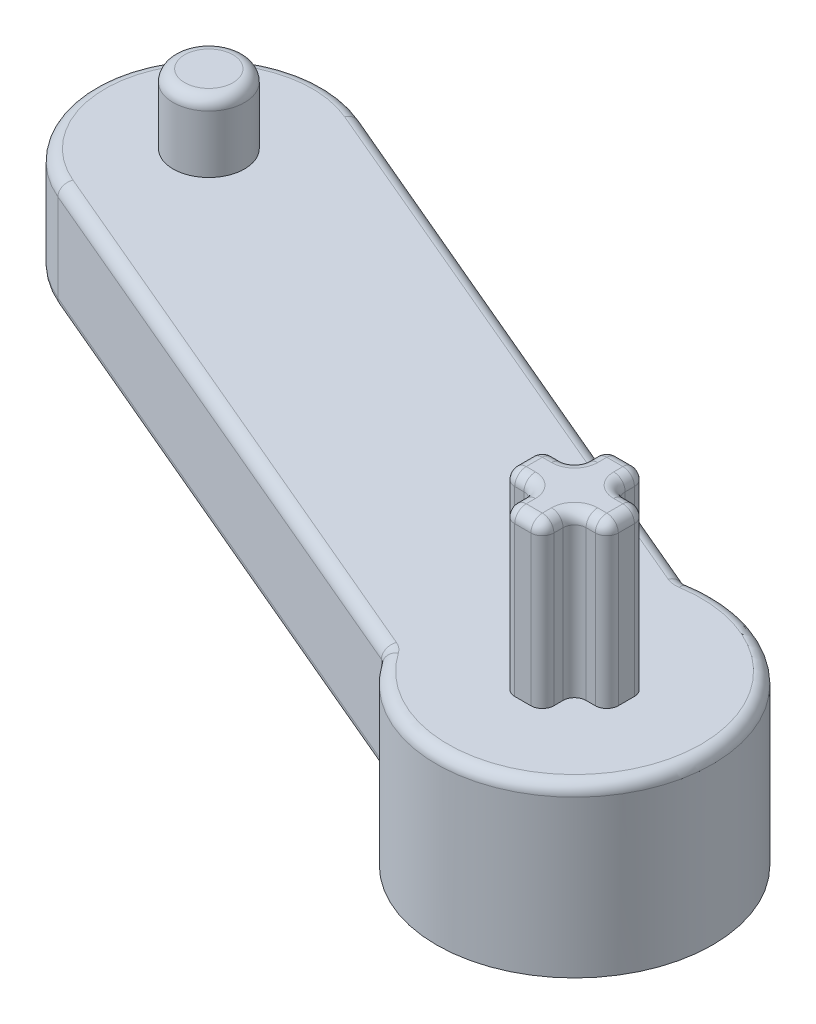
SolidWorks part; units mm, degrees
ref_plane "Front Plane" through (0, 0, 0) normal (0, 0, 1) x (1, 0, 0)
ref_plane "Top Plane" through (0, 0, 0) normal (0, 1, 0) x (1, 0, 0)
ref_plane "Right Plane" through (0, 0, 0) normal (1, 0, 0) x (0, 0, -1)
sketch "Sketch1" plane through (0, 0, 0) normal (0, 1, 0) x (1, 0, 0)
  line L1 (1.2678, 4.2969) -> (-1.2678, 4.2969) construction
  line L2 (1.2678, 4.2969) -> (1.2678, 2.6969) construction
  line L3 (1.2678, 2.6969) -> (-1.2678, 2.6969) construction
  line L4 (-1.2678, 4.2969) -> (-1.2678, 2.6969) construction
  line L5 (1.2678, 4.2969) -> (-1.2678, 2.6969) construction
  line L6 (1.2678, 2.6969) -> (-1.2678, 4.2969) construction
  line L7 (1.5678, 4.5156) -> (1.5678, 2.8811)
  line L8 (-1.5678, 2.8811) -> (-1.5678, 4.5156)
  line L10 (-1.5678, 4.5156) -> (-1.5678, 2.6969) construction
  circle A0 centre (0, 0) radius 2.98 construction
  arc A1 (-1.2678, 4.2969) -> (1.2678, 4.2969) centre (0, 0) cw construction
  arc A2 (1.2678, 2.6969) -> (-1.2678, 2.6969) centre (0, 0) cw construction
  arc A3 (-1.5678, 4.5156) -> (1.5678, 4.5156) centre (0, 0) cw
  arc A4 (-1.5678, 2.8811) -> (1.5678, 2.8811) centre (0, 0) ccw
  arc A5 (1.5678, 2.8811) -> (-1.3954, 2.9684) centre (0, 0) cw construction
  circle A6 centre (0, 0) radius 5.5
  circle A7 centre (0, 0) radius 4.78 construction
  point P3 (0, 3.4969)
  dimension "D1" = 1.6
  dimension "D3" = 5.96
  dimension "D5" = 11
  dimension "D2" = 4.48
  dimension "D4" = 0.3
extrude "Boss-Extrude1" add sketch "Sketch1" along normal blind 5.3
sketch "Sketch2" plane through (0, 5.3, 0) normal (0, 1, 0) x (1, 0, 0)
  circle A0 centre (0, 0) radius 6
  dimension "D1" = 12
extrude "Boss-Extrude2" add sketch "Sketch2" along normal blind 0.5
sketch "Sketch3" plane through (0, 5.8, 0) normal (0, 1, 0) x (1, 0, 0)
  line L0 (-0.85, -2.25) -> (-0.85, -0.85)
  line L1 (0.85, -2.25) -> (-0.85, -2.25)
  line L2 (0.85, -2.25) -> (0.85, 2.25) construction
  line L3 (0.85, 2.25) -> (-0.85, 2.25)
  line L4 (-0.85, -2.25) -> (-0.85, 2.25) construction
  line L5 (0.85, -2.25) -> (-0.85, 2.25) construction
  line L6 (0.85, 2.25) -> (-0.85, -2.25) construction
  line L7 (2.25, -0.85) -> (-2.25, -0.85) construction
  line L8 (2.25, -0.85) -> (2.25, 0.85)
  line L9 (2.25, 0.85) -> (-2.25, 0.85) construction
  line L10 (-2.25, -0.85) -> (-2.25, 0.85)
  line L11 (2.25, -0.85) -> (-2.25, 0.85) construction
  line L12 (2.25, 0.85) -> (-2.25, -0.85) construction
  line L13 (-0.85, -0.85) -> (-2.25, -0.85)
  line L14 (-2.25, 0.85) -> (-0.85, 0.85)
  line L15 (-0.85, 0.85) -> (-0.85, 2.25)
  line L16 (0.85, 2.25) -> (0.85, 0.85)
  line L17 (0.85, 0.85) -> (2.25, 0.85)
  line L18 (2.25, -0.85) -> (0.85, -0.85)
  line L19 (0.85, -0.85) -> (0.85, -2.25)
  line L21 (4, -4) -> (-4, -4) construction
  line L22 (4, -4) -> (4, 4) construction
  line L23 (4, 4) -> (-4, 4) construction
  line L24 (-4, -4) -> (-4, 4) construction
  line L25 (4, -4) -> (-4, 4) construction
  line L26 (4, 4) -> (-4, -4) construction
  circle A0 centre (-4, -4) radius 2.2 construction
  circle A1 centre (-4, 4) radius 2.2 construction
  circle A2 centre (4, 4) radius 2.2 construction
  circle A3 centre (4, -4) radius 2.2 construction
  point P0 (0, 0)
  point P6 (0, 0)
  point P11 (0, 0)
  dimension "D4" = 4.4
  dimension "D1" = 4.5
  dimension "D2" = 1.7
  dimension "D3" = 8
extrude "Boss-Extrude3" add sketch "Sketch3" along normal blind 8
sketch "Sketch4" plane through (0, 5.3, 0) normal (0, -1, 0) x (1, 0, 0)
  circle A0 centre (0, 0) radius 6
  circle A1 centre (0, 0) radius 5.5
  circle A2 centre (0, 0) radius 5.5 construction
  circle A3 centre (0, 0) radius 6 construction
extrude "Boss-Extrude4" add sketch "Sketch4" along normal up to surface (5.3 mm away) up to face at (0, 0, 5.5)
sketch "Sketch5" plane through (0, 13.8, 0) normal (0, 1, 0) x (1, 0, 0)
  circle A0 centre (0, 0) radius 2.4052
extrude "Cut-Extrude1" cut sketch "Sketch5" against normal blind 1
sketch "Sketch6" plane through (0, 0, 0) normal (0, -1, 0) x (1, 0, 0)
  line L0 (0, 0) -> (-15.3335, -6.5103) construction
  line L1 (-29.5682, -7.1221) -> (-25.66, -16.3268) construction
  line L2 (-29.5682, -7.1221) -> (-5.0069, 3.3062)
  line L3 (-5.0069, 3.3062) -> (-1.0988, -5.8985) construction
  line L4 (-25.66, -16.3268) -> (-1.0988, -5.8985)
  line L5 (-29.5682, -7.1221) -> (-1.0988, -5.8985) construction
  line L6 (-5.0069, 3.3062) -> (-25.66, -16.3268) construction
  line L7 (-5.5228, -2.3449) -> (-27.6141, -11.7244) construction
  circle A0 centre (0, 0) radius 6 construction
  arc A2 (-29.5682, -7.1221) -> (-25.66, -16.3268) centre (-27.6141, -11.7244) ccw
  arc A3 (-1.0988, -5.8985) -> (-5.0069, 3.3062) centre (0, 0) cw
  arc A5 (-28.7737, -3.0286) -> (-28.2774, -3.525) centre (-24.9987, 0.25) ccw construction
  point P0 (-15.3335, -6.5103)
  circle M3 centre (0, 0) radius 6
  dimension "D2" = 10
  dimension "D1" = 30
extrude "Boss-Extrude5" add sketch "Sketch6" against normal up to surface (5.8 mm away) contours L2 A2 L4 M3 | L2 A2 L4 A3 region at (-18.0205, 0, -7.6512) up to face at (0, 5.8, 0)
sketch "Sketch7" plane through (0, 5.8, 0) normal (0, 1, 0) x (1, 0, 0)
  circle A0 centre (-27.6141, 11.7244) radius 1.55
  dimension "D1" = 3.1
extrude "Boss-Extrude6" add sketch "Sketch7" along normal blind 3
sketch "Sketch9" plane through (0, 0, 0) normal (0, -1, 0) x (1, 0, 0)
  line L0 (-1.5678, -4.5156) -> (-1.5678, -2.8811) construction
  line L1 (-1.5678, -2.8811) -> (-1.5678, -4.5156)
  line L2 (1.5678, -2.8811) -> (1.5678, -4.5156)
  arc A0 (1.5678, -2.8811) -> (-1.5678, -2.8811) centre (0, 0) ccw
  arc A1 (1.5678, -4.5156) -> (-1.5678, -4.5156) centre (0, 0) cw
  arc A2 (-1.5678, -4.5156) -> (1.5678, -4.5156) centre (0, 0) ccw construction
  circle A3 centre (0, 0) radius 6
  dimension "D1" = 12
extrude "Boss-Extrude7" add sketch "Sketch9" along normal up to surface (1.5 mm away)
sketch "Sketch10" plane through (0, 0, 0) normal (0, -1, 0) x (1, 0, 0)
  line L1 (-1.0988, -5.8985) -> (-25.66, -16.3268)
  line L2 (-5.0069, 3.3062) -> (-29.5682, -7.1221)
  arc A0 (-5.0069, 3.3062) -> (-1.0988, -5.8985) centre (0, 0) ccw
  arc A1 (-25.66, -16.3268) -> (-29.5682, -7.1221) centre (-27.6141, -11.7244) cw
  arc A2 (-5.0069, 3.3062) -> (-1.0988, -5.8985) centre (0, 0) ccw construction
extrude "Cut-Extrude2" cut sketch "Sketch10" against normal blind 1
fillet "Fillet1" radius 0.5 39 edges at (-0.85, 9.3, 0.85) (0.85, 9.3, -2.25) (2.25, 9.3, -0.85) (0.85, 9.3, -0.85) (-0.85, 9.3, -0.85) (-0.85, 9.3, -2.25) (2.25, 9.3, 0.85) (0.85, 9.3, 2.25) (-2.25, 9.3, -0.85) (-0.85, 9.3, 2.25) (-2.25, 9.3, 0.85) (-1.5678, 1.9, -2.8811) (-1.5678, 1.9, -4.5156) (1.5678, 1.9, -4.5156) (1.5678, 1.9, -2.8811) (0.85, 9.3, 0.85) (0, 12.8, -2.25) (0.85, 12.8, -1.55) (1.55, 12.8, -0.85) (2.25, 12.8, 0) (1.55, 12.8, 0.85) (0.85, 12.8, 1.55) (0, 12.8, 2.25) (-0.85, 12.8, 1.55) (-1.55, 12.8, 0.85) (-2.25, 12.8, 0) (-1.55, 12.8, -0.85) (-0.85, 12.8, -1.55) (5.5228, 5.8, 2.3449) (-17.2875, 5.8, -1.908) (-32.2164, 5.8, -13.6785) (-27.6141, 8.8, -10.1744) (-13.3794, 5.8, -11.1127) (-1.0988, 3.4, -5.8985) (-5.0069, 3.4, 3.3062) (-13.3794, 1, -11.1127) (-32.2164, 1, -13.6785) (-17.2875, 1, -1.908) (-5.5228, 1, -2.3449)
equation "\"Bearing Inner Diameter\"= 3.1mm"
equation "\"Bearing Outer Diameter\" = 7.25mm"
equation "\"ArmLength\" = 25mm"
equation "\"ArmLength2\" = 30mm"
equation "\"D1@Sketch6\"=\"ArmLength2\""
equation "\"D1@Sketch7\"=\"Bearing Inner Diameter\""
